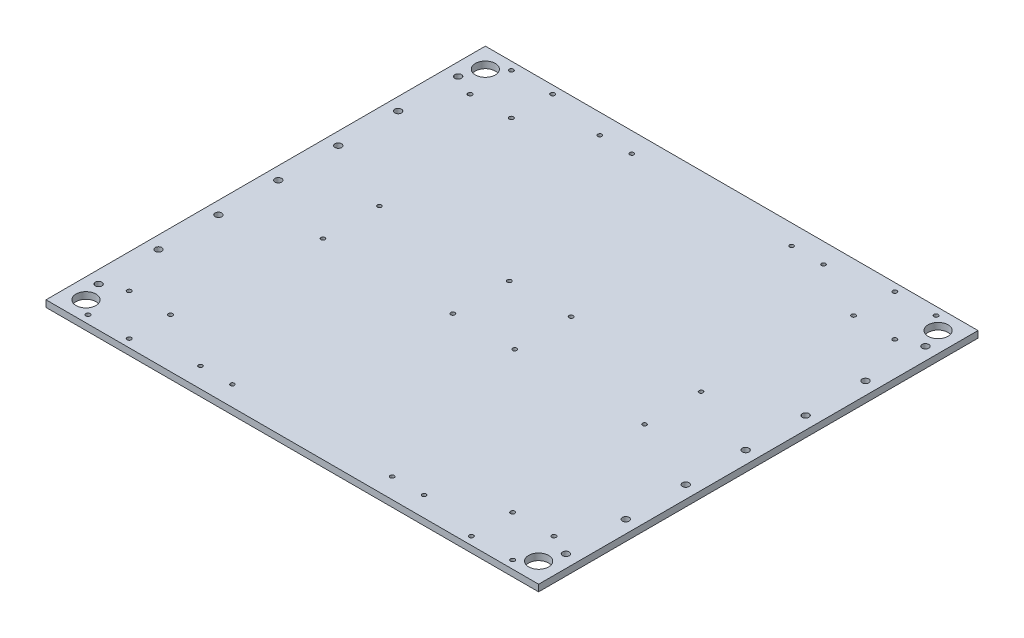
SolidWorks part; units mm, degrees
ref_plane "前视基准面" through (0, 0, 0) normal (0, 0, 1) x (1, 0, 0)
ref_plane "上视基准面" through (0, 0, 0) normal (0, 1, 0) x (1, 0, 0)
ref_plane "右视基准面" through (0, 0, 0) normal (1, 0, 0) x (0, 0, -1)
other "Configuration Table"
sketch "草图1" plane through (0, 0, 0) normal (0, 1, 0) x (1, 0, 0)
  line L1 (185, -165) -> (-185, -165)
  line L2 (185, -165) -> (185, 165)
  line L3 (185, 165) -> (-185, 165)
  line L4 (-185, -165) -> (-185, 165)
  line L5 (185, -165) -> (-185, 165) construction
  line L6 (185, 165) -> (-185, -165) construction
  point P0 (0, 0)
  dimension "D1" = 370
  dimension "D2" = 330
extrude "凸台-拉伸1" add sketch "草图1" along normal blind 5
sketch "草图2" plane through (0, 5, 0) normal (0, 1, 0) x (1, 0, 0)
  circle A0 centre (-159.5, 159) radius 1.6
  circle A1 centre (-128.5, 159) radius 1.6
  circle A2 centre (-159.5, 128) radius 1.6022
  circle A3 centre (-128.5, 128) radius 1.6
  circle A4 centre (128.5, 159) radius 1.6
  circle A5 centre (159.5, 159) radius 1.6
  circle A6 centre (128.5, 128) radius 1.6
  circle A7 centre (159.5, 128) radius 1.6
  circle A8 centre (128.5, -128) radius 1.6
  circle A9 centre (159.5, -128) radius 1.6
  circle A10 centre (159.5, -159) radius 1.6
  circle A11 centre (128.5, -159) radius 1.6
  circle A12 centre (-128.5, -159) radius 1.6
  circle A13 centre (-159.5, -159) radius 1.6
  circle A14 centre (-159.5, -128) radius 1.6
  circle A15 centre (-128.5, -128) radius 1.6
extrude "切除-拉伸1" cut sketch "草图2" against normal through all
sketch "草图3" plane through (0, 5, 0) normal (0, 1, 0) x (1, 0, 0)
  line L0 (-110, 60) -> (-110, 40)
  line L1 (110, -110) -> (-110, -110) construction
  line L2 (110, -110) -> (110, 110) construction
  line L3 (110, 110) -> (-110, 110) construction
  line L4 (-110, -110) -> (-110, 110) construction
  line L5 (110, -110) -> (-110, 110) construction
  line L6 (110, 110) -> (-110, -110) construction
  line L7 (-110, 110) -> (110, 110)
  line L8 (-110, 110) -> (-110, 90)
  line L9 (-110, 90) -> (110, 90)
  line L10 (110, 110) -> (110, 90)
  line L11 (-110, 60) -> (110, 60)
  line L12 (110, 60) -> (110, 40)
  line L13 (-110, 40) -> (110, 40)
  line L14 (-110, 10) -> (-110, -10)
  line L15 (-110, 10) -> (110, 10)
  line L16 (110, 10) -> (110, -10)
  line L17 (-110, -10) -> (110, -10)
  line L18 (-110, -40) -> (-110, -60)
  line L19 (-110, -40) -> (110, -40)
  line L20 (110, -40) -> (110, -60)
  line L21 (-110, -60) -> (110, -60)
  line L22 (-110, -90) -> (-110, -110)
  line L23 (-110, -90) -> (110, -90)
  line L24 (110, -90) -> (110, -110)
  line L25 (-110, -110) -> (110, -110)
  point P0 (0, 0)
  dimension "D1" = 220
  dimension "D2" = 220
  dimension "D3" = 20
  dimension "D4" = 5
extrude "切除-拉伸2" cut sketch "草图3" against normal through all contours L10 L7 L8 L9 | L0 L13 L12 L11 | L14 L17 L16 L15 | L18 L21 L20 L19 | L22 L25 L24 L23 | L8 L7 L10 L9 | L0 L13 L12 L11 region at (0, 5, -50) region at (0, 5, -100) region at (0, 5, 0) region at (0, 5, 50) region at (0, 5, 100)
sketch "草图8" plane through (0, 5, 0) normal (0, 1, 0) x (1, 0, 0)
  line L0 (120, 0) -> (-120, 0)
  line L1 (0, -120) -> (0, 120)
  point P4 (0, 0)
  point P8 (0, 0)
sketch "草图9" plane through (0, 5, 0) normal (0, 1, 0) x (1, 0, 0)
  line L1 (-117.6798, 117.0824) -> (121.8613, 117.0824)
  line L2 (-117.6798, 117.0824) -> (-117.6798, -116.4851)
  line L3 (-117.6798, -116.4851) -> (121.8613, -116.4851)
  line L4 (121.8613, 117.0824) -> (121.8613, -116.4851)
extrude "凸台-拉伸2" add sketch "草图9" against normal blind 5
sketch "草图12" plane through (0, 5, 0) normal (0, 1, 0) x (1, 0, 0)
  line L0 (185, 0) -> (175.5, 0) construction
  line L1 (185, -165) -> (185, 165) construction
  line L2 (0, -120) -> (0, 120) construction
  line L3 (120, 0) -> (-120, 0) construction
  line L4 (0, -120) -> (0, 120)
  line L5 (120, 0) -> (-120, 0)
  line L6 (-185, 0) -> (-175.5, 0) construction
  circle A0 centre (175.5, 0) radius 2.5
  circle A1 centre (175.5, 45) radius 2.5
  circle A2 centre (175.5, 90) radius 2.5
  circle A3 centre (175.5, 135) radius 2.5
  circle A4 centre (175.5, -135) radius 2.5
  circle A5 centre (175.5, -90) radius 2.5
  circle A6 centre (175.5, -45) radius 2.5
  circle A7 centre (-175.5, -45) radius 2.5
  circle A8 centre (-175.5, -90) radius 2.5
  circle A9 centre (-175.5, -135) radius 2.5
  circle A10 centre (-175.5, 135) radius 2.5
  circle A11 centre (-175.5, 90) radius 2.5
  circle A12 centre (-175.5, 45) radius 2.5
  circle A13 centre (-175.5, 0) radius 2.5
  dimension "D2" = 5
  dimension "D1" = 9.5
  dimension "D3" = 4
extrude "切除-拉伸6" cut sketch "草图12" against normal blind 10 contours A9 | A8 | A7 | A13 | A12 | A11 | A10 | A4 | A5 | A6 | A0 | A1 | A2 | A3 region at (175.5, 5, 0) region at (175.5, 5, -45) region at (175.5, 5, -90) region at (175.5, 5, -135) region at (175.5, 5, 135) region at (175.5, 5, 90) region at (175.5, 5, 45) region at (-175.5, 5, 45) region at (-175.5, 5, 90) region at (-175.5, 5, 135) region at (-175.5, 5, -135) region at (-175.5, 5, -90) region at (-175.5, 5, -45) region at (-175.5, 5, 0)
sketch "草图13" plane through (0, 5, 0) normal (0, 1, 0) x (1, 0, 0)
  line L0 (120, 0) -> (-120, 0) construction
  line L1 (-185, -165) -> (-170, -165)
  line L2 (-185, -165) -> (-185, -150)
  line L3 (-185, -150) -> (-170, -150)
  line L4 (-170, -165) -> (-170, -150)
  line L5 (0, -120) -> (0, 120) construction
  line L6 (120, 0) -> (-120, 0)
  line L7 (0, -120) -> (0, 120)
  circle A1 centre (-170, -150) radius 7.5
  circle A2 centre (170, -150) radius 7.5
  circle A3 centre (170, 150) radius 7.5
  circle A4 centre (-170, 150) radius 7.5
  dimension "D3" = 15
  dimension "D1" = 15
  dimension "D2" = 15
extrude "切除-拉伸7" cut sketch "草图13" against normal blind 10 contours A2 | L4 A1 L3 | L3 A1 L4 | A4 | A3 region at (-173.1831, 5, 153.1831) region at (-168.939, 5, 148.939) region at (170, 5, 150) region at (170, 5, -150) region at (-170, 5, -150)
sketch "草图14" plane through (0, 5, 0) normal (0, 1, 0) x (1, 0, 0)
  line L0 (-77.3344, 165) -> (-77.3344, 155) construction
  line L1 (185, 165) -> (-185, 165) construction
  line L2 (-185, 165) -> (-185, -165) construction
  line L3 (-185, 140) -> (-142, 140) construction
  line L4 (-108.7902, 140) -> (-29.7478, 140) construction
  line L5 (-142, 140) -> (-142, 94.5665) construction
  line L6 (-142, 140) -> (-2, 140)
  line L7 (-142, 140) -> (-142, 0)
  line L8 (-142, 0) -> (-2, 0)
  line L9 (-2, 140) -> (-2, 0)
  line L10 (-142, 140) -> (-84, 140) construction
  line L11 (-84, 140) -> (-84, 150) construction
  line L12 (-142, 140) -> (-2, 0) construction
  line L13 (-2, 140) -> (-142, 0) construction
  line L14 (120, 0) -> (-120, 0) construction
  line L15 (0, -120) -> (0, 120) construction
  line L16 (120, 0) -> (-120, 0)
  line L17 (0, -120) -> (0, 120)
  circle A0 centre (-84, 150) radius 1.505
  circle A1 centre (-60, 150) radius 1.505
  circle A2 centre (-120.7868, 21.2132) radius 1.505
  circle A3 centre (-23.2132, 21.2132) radius 1.55
  circle A4 centre (23.2132, 21.2132) radius 1.55
  circle A5 centre (120.7868, 21.2132) radius 1.505
  circle A6 centre (84, 150) radius 1.505
  circle A7 centre (60, 150) radius 1.505
  circle A8 centre (84, -150) radius 1.505
  circle A9 centre (60, -150) radius 1.505
  circle A10 centre (120.7868, -21.2132) radius 1.505
  circle A11 centre (23.2132, -21.2132) radius 1.55
  circle A12 centre (-23.2132, -21.2132) radius 1.55
  circle A13 centre (-120.7868, -21.2132) radius 1.505
  circle A14 centre (-84, -150) radius 1.505
  circle A15 centre (-60, -150) radius 1.505
  point P48 (-60, -150)
  dimension "D8" = 3.01
  dimension "D9" = 3.01
  dimension "D11" = 3.01
  dimension "D12" = 3.1
  dimension "D1" = 10
  dimension "D2" = 43
  dimension "D3" = 15
  dimension "D4" = 140
  dimension "D5" = 140
  dimension "D6" = 58
  dimension "D7" = 10
  dimension "D10" = 24
  dimension "D13" = 30
  dimension "D14" = 30
extrude "切除-拉伸8" cut sketch "草图14" against normal blind 10 contours A0 | A1 | A13 | A2 | A3 | A4 | A10 | A5 | A7 | A6 | A14 | A15 | A9 | A8 | A12 | A11 region at (-84, 5, -150) region at (-60, 5, -150) region at (-120.7868, 5, -21.2132) region at (-23.2132, 5, -21.2132) region at (23.2132, 5, -21.2132) region at (120.7868, 5, -21.2132) region at (84, 5, -150) region at (60, 5, -150) region at (84, 5, 150) region at (60, 5, 150) region at (120.7868, 5, 21.2132) region at (-120.7868, 5, 21.2132) region at (-84, 5, 150) region at (-60, 5, 150)
